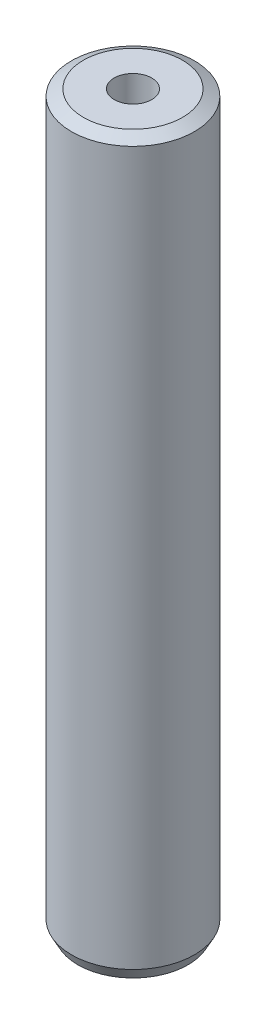
SolidWorks part; units mm, degrees
ref_plane "Front Plane" through (0, 0, 0) normal (0, 0, 1) x (1, 0, 0)
ref_plane "Top Plane" through (0, 0, 0) normal (0, 1, 0) x (1, 0, 0)
ref_plane "Right Plane" through (0, 0, 0) normal (1, 0, 0) x (0, 0, -1)
sketch "Sketch1" plane through (0, 0, 0) normal (0, 1, 0) x (1, 0, 0)
  circle A0 centre (0, 0) radius 22.5
  dimension "SHAFT_OD" = 45
extrude "Boss-Extrude1" add sketch "Sketch1" along normal blind 267.6304
sketch "Sketch2" plane through (0, 0, 0) normal (0, 1, 0) x (1, 0, 0)
  circle A0 centre (0, 0) radius 6.8749
  dimension "BORE_D" = 13.7498
extrude "Cut-Extrude1" cut sketch "Sketch2" along normal through all
chamfer "Chamfer1" distance 2.3417 angle 61.716 2 edges at (0, 267.6304, 22.5) (0, 0, 22.5) first distance on face at (0, 267.6304, 22.5) first distance on face at (0, 0, 6.8749)
